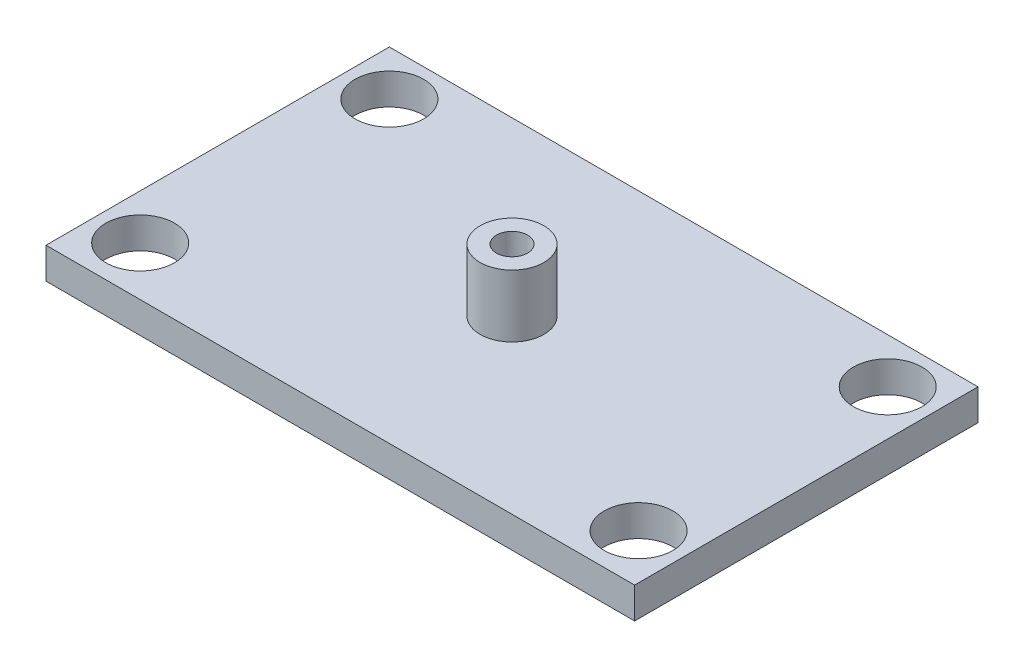
SolidWorks part; units mm, degrees
ref_plane "Front Plane" through (0, 0, 0) normal (0, 0, 1) x (1, 0, 0)
ref_plane "Top Plane" through (0, 0, 0) normal (0, 1, 0) x (1, 0, 0)
ref_plane "Right Plane" through (0, 0, 0) normal (1, 0, 0) x (0, 0, -1)
sketch "Sketch1" plane through (0, 0, 0) normal (0, 1, 0) x (1, 0, 0)
  line L0 (4.6, 30.4) -> (0, 30.4) construction
  line L1 (0, 0) -> (60, 0)
  line L2 (0, 0) -> (0, 35)
  line L3 (0, 35) -> (60, 35)
  line L4 (60, 0) -> (60, 35)
  line L5 (4.6, 30.4) -> (55.4, 30.4) construction
  line L6 (4.6, 30.4) -> (4.6, 5) construction
  line L7 (4.6, 5) -> (55.4, 5) construction
  line L8 (55.4, 30.4) -> (55.4, 5) construction
  line L9 (4.6, 30.4) -> (4.6, 35) construction
  circle A0 centre (4.6, 30.4) radius 3.5
  circle A1 centre (55.4, 30.4) radius 3.5
  circle A2 centre (4.6, 5) radius 3.5
  circle A3 centre (55.4, 5) radius 3.5
  circle A4 centre (30, 17.5) radius 1.25
  point P13 (30, 30.4)
  point P14 (30, 35)
  point P20 (60, 17.5)
  dimension "D5" = 7
  dimension "D6" = 2.5
  dimension "D1" = 60
  dimension "D2" = 35
  dimension "D3" = 50.8
  dimension "D4" = 25.4
extrude "Boss-Extrude1" add sketch "Sketch1" along normal blind 9.525
sketch "Sketch2" plane through (0, 9.525, 0) normal (0, 1, 0) x (1, 0, 0)
  line L1 (0, 0) -> (60, 0)
  line L2 (0, 0) -> (0, 35)
  line L3 (0, 35) -> (60, 35)
  line L4 (60, 0) -> (60, 35)
  circle A0 centre (30, 17.5) radius 3.25
  dimension "D1" = 6.5
extrude "Cut-Extrude1" cut sketch "Sketch2" against normal blind 6.35
sketch "Sketch4" plane through (0, 9.525, 0) normal (0, 1, 0) x (1, 0, 0)
  circle A0 centre (30, 17.5) radius 1.59
  dimension "D1" = 3.18
extrude "Cut-Extrude2" cut sketch "Sketch4" against normal blind 6.35
